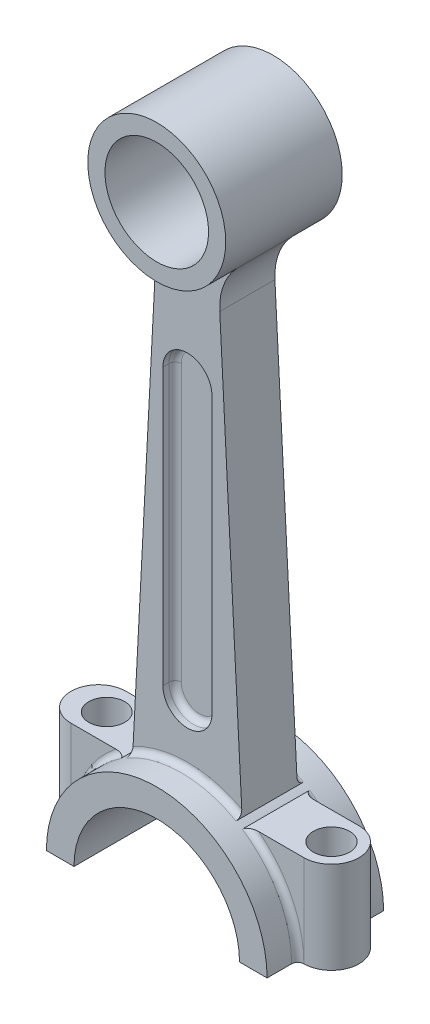
SolidWorks part; units mm, degrees
ref_plane "Front Plane" through (0, 0, 0) normal (0, 0, 1) x (1, 0, 0)
ref_plane "Top Plane" through (0, 0, 0) normal (0, 1, 0) x (1, 0, 0)
ref_plane "Right Plane" through (0, 0, 0) normal (1, 0, 0) x (0, 0, -1)
sketch "Sketch1" plane through (0, 0, 0) normal (0, 0, 1) x (1, 0, 0)
  line L0 (0, 0) -> (0, 308.0923) construction
  line L1 (10, 181.0444) -> (17.8497, 31.2632)
  line L2 (-10, 181.0444) -> (-17.8497, 31.2632)
  line L3 (-36, 0) -> (-27, 0)
  line L4 (27, 0) -> (36, 0)
  arc A0 (-27, 0) -> (27, 0) centre (0, 0) cw
  arc A1 (-36, 0) -> (36, 0) centre (0, 0) cw
  circle A2 centre (0, 201.2) radius 16.9
  circle A3 centre (0, 201.2) radius 22.5
  dimension "D1" = 27
  dimension "D2" = 36
  dimension "D3" = 45
  dimension "D4" = 33.8
  dimension "D5" = 10
  dimension "D6" = 3
  dimension "D7" = 201.2
extrude "Boss-Extrude1" add sketch "Sketch1" along normal mid plane 38 contours A3 L0 A2 | L0 A3 A2 | L0 A0 L4 A1 | A0 L0 A1 L3 region at (-20.1899, 20.1899, 0) region at (20.1899, 20.1899, 0) region at (-5.0207, 179.7838, 0) region at (0.5031, 181.5, 0)
extrude "Boss-Extrude2" add sketch "Sketch1<3>" along normal mid plane 18 contours A1 L0 A3 L2 | L0 A1 L1 A3 region at (-7.1843, 100.3545, 0) region at (7.1843, 100.3545, 0)
sketch "Sketch1<3>" plane through (0, 0, 0) normal (0, 0, 1) x (1, 0, 0) same geometry as "Sketch1"
sketch "Sketch2" plane through (0, 0, -9) normal (0, 0, -1) x (-1, 0, 0)
  line L0 (0, 145.6) -> (0, 55.6) construction
  line L1 (8, 145.6) -> (8, 55.6)
  line L2 (-8, 145.6) -> (-8, 55.6)
  arc A0 (8, 145.6) -> (-8, 145.6) centre (0, 145.6) ccw
  arc A1 (-8, 55.6) -> (8, 55.6) centre (0, 55.6) ccw
  point P3 (0, 100.6)
  dimension "D3" = 8
  dimension "D1" = 100.6
  dimension "D2" = 90
extrude "Cut-Extrude1" cut sketch "Sketch2" against normal blind 4
mirror "Mirror1" about plane through (0, 0, 0) normal (0, 0, 1) of "Cut-Extrude1"
fillet "Fillet1" radius 2 8 edges at (8, 100.6, 5) (0, 47.6, 5) (-8, 100.6, 5) (0, 153.6, 5) (-8, 100.6, -5) (0, 47.6, -5) (8, 100.6, -5) (0, 153.6, -5)
fillet "Fillet2" radius 20 2 edges at (-10, 181.0444, 0) (10, 181.0444, 0)
ref_plane "Plane1" through (0, 30, 0) normal (0, -1, 0) x (-1, 0, 0)
sketch "Sketch3" plane through (0, 30, 0) normal (0, -1, 0) x (-1, 0, 0)
  line L0 (-36, 0) -> (35.3055, 0) construction
  line L1 (-36, -19) -> (-36, 19) construction
  line L2 (-38, 0) -> (38, 0) construction
  line L3 (-38, 9) -> (38, 9)
  line L4 (-38, -9) -> (38, -9)
  arc A0 (-38, 9) -> (-38, -9) centre (-38, 0) ccw
  arc A1 (38, -9) -> (38, 9) centre (38, 0) ccw
  circle A2 centre (-38, 0) radius 5.9186
  circle A3 centre (35.3055, 0) radius 5.8696
  point P6 (0, 0)
  point P11 (0, 9)
  dimension "D2" = 9
  dimension "D1" = 76
extrude "Boss-Extrude3" add sketch "Sketch3" along normal blind 30
sketch "Sketch4" plane through (0, 0, -9) normal (0, 0, -1) x (-1, 0, 0)
  line L0 (-27, 0) -> (27, 0)
  arc A0 (-27, 0) -> (27, 0) centre (0, 0) cw
extrude "Cut-Extrude2" cut sketch "Sketch4" against normal through all
sketch "Sketch5" plane through (0, 30, 0) normal (0, 1, 0) x (1, 0, 0)
  circle A0 centre (-35.3055, 0) radius 5.8696
  circle A1 centre (38, 0) radius 5.9186
  circle A2 centre (-35.3055, 0) radius 5.8696 construction
  circle A3 centre (38, 0) radius 5.9186 construction
extrude "Cut-Extrude3" cut sketch "Sketch5" against normal through all
fillet "Fillet3" radius 2 6 edges at (-31.7206, 17.0236, -9) (0, 36, -9) (31.7206, 17.0236, -9) (31.7206, 17.0236, 9) (-31.7206, 17.0236, 9) (0, 36, 9)
